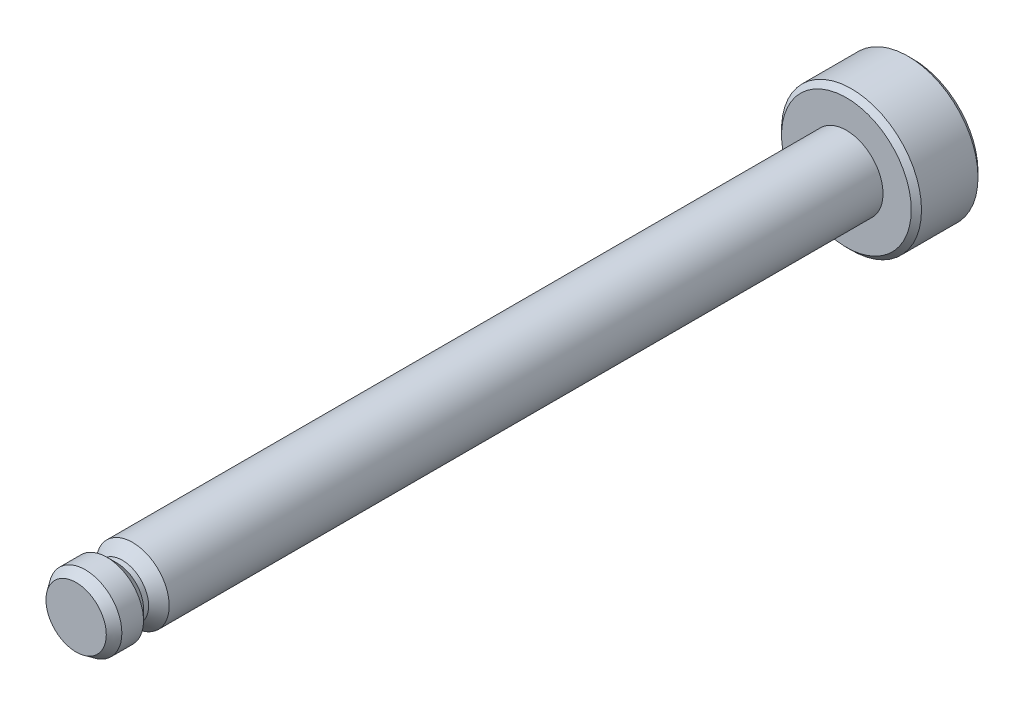
SolidWorks part; units mm, degrees
ref_plane "Front" through (0, 0, 0) normal (0, 0, 1) x (1, 0, 0)
ref_plane "Top" through (0, 0, 0) normal (0, 1, 0) x (1, 0, 0)
ref_plane "Right" through (0, 0, 0) normal (1, 0, 0) x (0, 0, -1)
sketch "Sketch2" plane through (0, 0, 0) normal (0, 0, 1) x (1, 0, 0)
  circle A0 centre (0, 0) radius 1.425
  dimension "D1" = 2.85
extrude "Shaft" add sketch "Sketch2" along normal blind 30
sketch "Sketch5" plane through (0, 0, 0) normal (0, 0, 1) x (1, 0, 0)
  circle A0 centre (0, 0) radius 2.725
  dimension "D1" = 5.45
extrude "Head" add sketch "Sketch5" against normal blind 2.6
sketch "Sketch4" plane through (0, 0, 0) normal (1, 0, 0) x (0, 0, -1)
  line L0 (0, 0) -> (-28.3, 0) construction
  line L1 (-28.3, 0) -> (-28.3, 4.3666) construction
  line L2 (-28.8, 1.425) -> (-27.8, 1.425)
  line L3 (0, 1.425) -> (-30, 1.425) construction
  line L6 (-27.8, 1.425) -> (-28.2, 1.025)
  line L7 (-28.2, 1.025) -> (-28.4, 1.025)
  line L8 (-28.4, 1.025) -> (-28.8, 1.425)
  line L9 (-28.3, 50) -> (-28.3, -50) construction
  dimension "D2" = 1
  dimension "D3" = 45
  dimension "D4" = 0.4
revolve "e-Clip Notch Short" [suppressed] cut sketch "Sketch4" angle 360 about L0
chamfer "Chamfer1" distance 0.25 angle 55 1 edges at (1.425, 0, 30) first distance on face at (1.425, 0, 30)
chamfer "Deburs" distance 0.2 angle 45 2 edges at (2.725, 0, 0) (2.725, 0, -2.6)
sketch "Sketch6" plane through (0, 0, 0) normal (1, 0, 0) x (0, 0, -1)
  line L0 (0, 0) -> (-28.3, 0) construction
  line L1 (-28.3, 0) -> (-28.3, 1.025) construction
  line L2 (0, 1.425) -> (-29.643, 1.425) construction
  line L3 (-28.8, 1.425) -> (-27.8, 1.425)
  line L4 (-27.8, 1.425) -> (-28.2, 1.025)
  line L5 (-28.2, 1.025) -> (-28.4, 1.025)
  line L6 (-28.4, 1.025) -> (-28.8, 1.425)
  line L7 (-28.3, 1.025) -> (-28.3, 1.425) construction
  line L8 (-28.8, 1.425) -> (-27.8, 1.425) construction
  line L9 (-28.4, 1.025) -> (-28.8, 1.425) construction
revolve "e-Clip Notch Long" cut sketch "Sketch6" angle 360 about L0
equation "\"D1@Sketch2\"=\"Hardware Clearance Hole Diameter@Box Assy.Assembly\"-.3"
equation "\"D1@Sketch5\"=\"Hardware Head Countersink Diameter@Box Assy.Assembly\"-.3mm"
equation "\"D1@Head\"=\"Nut Trap Depth@Box Assy.Assembly\""
